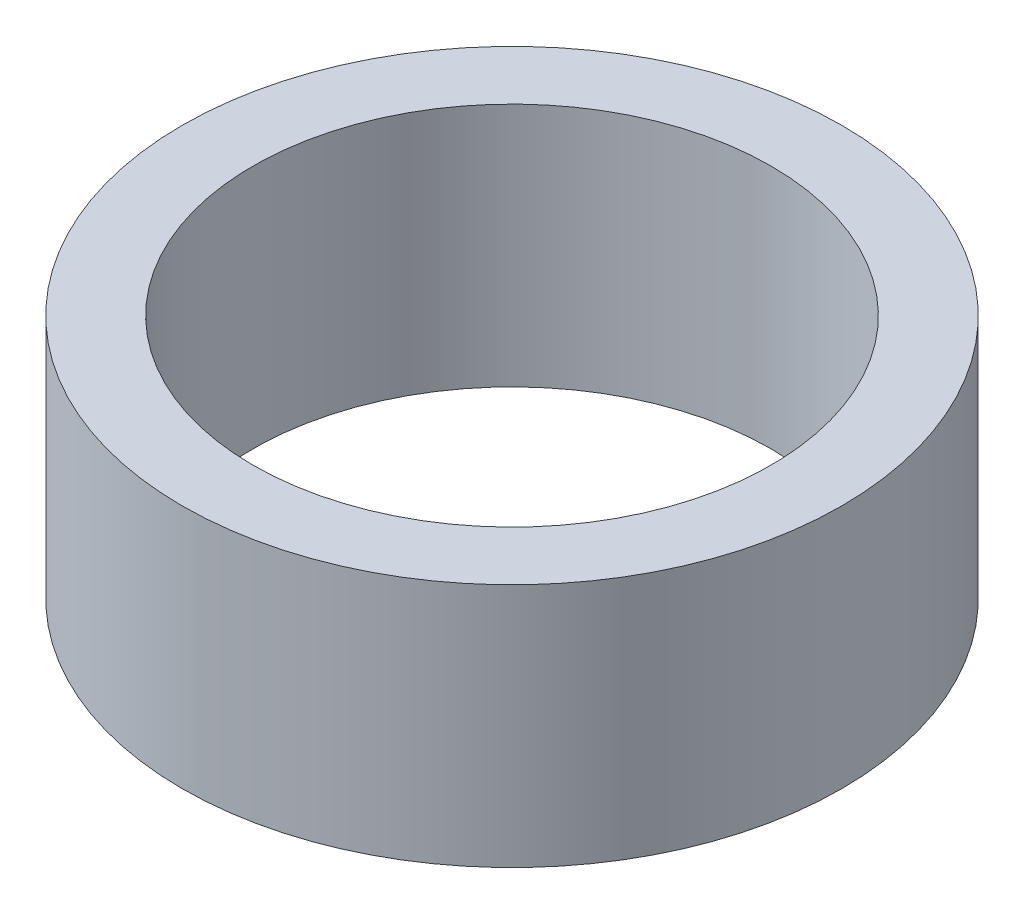
SolidWorks part; units mm, degrees
ref_plane "Front Plane" through (0, 0, 0) normal (0, 0, 1) x (1, 0, 0)
ref_plane "Top Plane" through (0, 0, 0) normal (0, 1, 0) x (1, 0, 0)
ref_plane "Right Plane" through (0, 0, 0) normal (1, 0, 0) x (0, 0, -1)
sketch "Sketch1" plane through (0, 0, 0) normal (0, 1, 0) x (1, 0, 0)
  circle A0 centre (0, 0) radius 35
  dimension "FLANGE_OD" = 70
extrude "Boss-Extrude1" add sketch "Sketch1" along normal blind 26
sketch "Sketch2" plane through (0, 0, 0) normal (0, 1, 0) x (1, 0, 0)
  circle A0 centre (0, 0) radius 27.5
  dimension "BORE_D" = 55
extrude "Cut-Extrude1" cut sketch "Sketch2" along normal through all
sketch "Sketch3" plane through (0, 26, 0) normal (0, 1, 0) x (1, 0, 0)
  circle A0 centre (0, 0) radius 15.7819 construction
  circle A1 centre (-15.7819, 0) radius 1.5
  dimension "BOLT_D" = 3
  dimension "BOLT_PCD" = 31.5638
extrude "Cut-Extrude2" cut sketch "Sketch3" against normal blind 16.557 rebuild error yes
pattern_circular "CirPattern1" count 5 over 360 rebuild error yes
